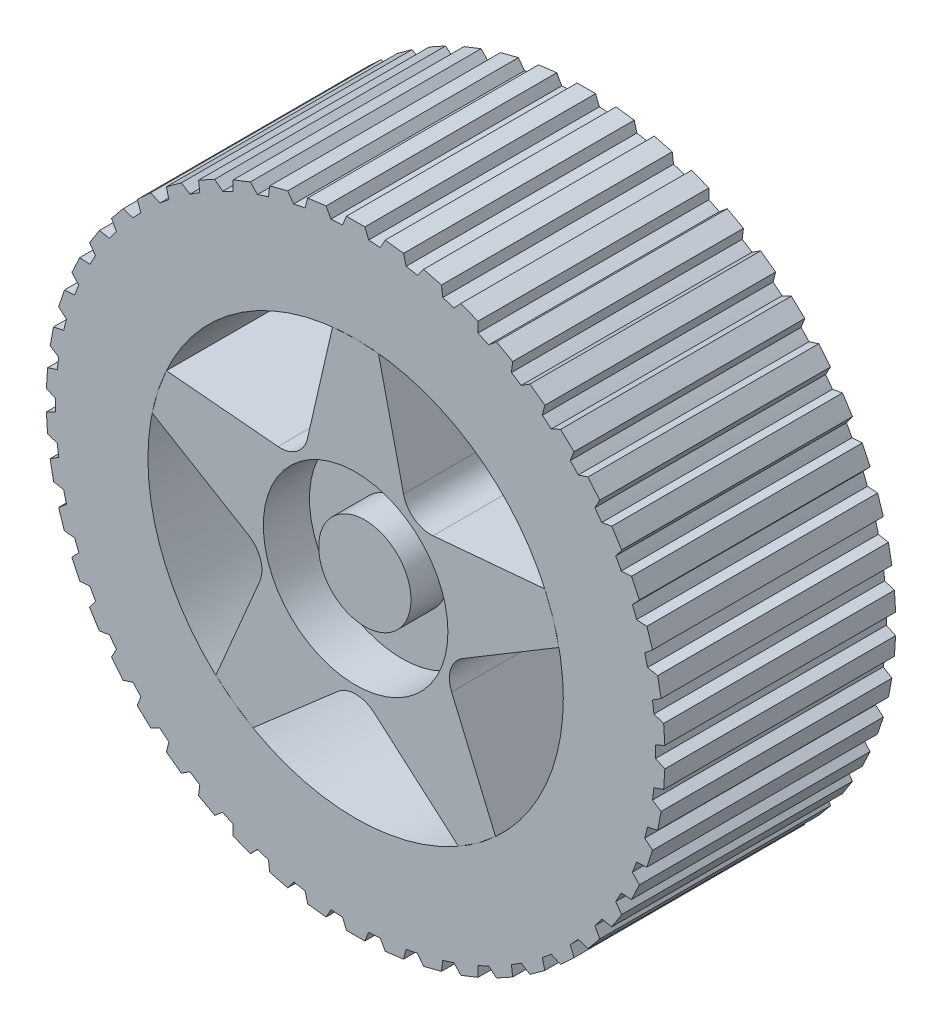
SolidWorks part; units mm, degrees
note: The reader was unsure of these and kept them because the rebuilt part matched: shared geometry of "Sketch1<13>", "Sketch1<14>".
ref_plane "Front Plane" through (0, 0, 0) normal (0, 0, 1) x (1, 0, 0)
ref_plane "Top Plane" through (0, 0, 0) normal (0, 1, 0) x (1, 0, 0)
ref_plane "Right Plane" through (0, 0, 0) normal (1, 0, 0) x (0, 0, -1)
sketch "Sketch1" plane through (0, 0, 0) normal (0, 0, 1) x (1, 0, 0)
  line L1 (0, 22.5) -> (-2.4961, 22.3611)
  line L3 (0, 22.5) -> (2.4961, 22.3611)
  line L4 (-2.4961, 22.3611) -> (-5.221, 10.5079)
  line L8 (2.4715, 22.3638) -> (5.1922, 10.5288)
  line L9 (20.4953, 9.2839) -> (8.3802, 8.2126)
  line L10 (21.3988, 6.9529) -> (20.4953, 9.2839)
  line L11 (21.3988, 6.9529) -> (22.038, 4.536)
  line L12 (22.033, 4.5602) -> (11.618, -1.6845)
  line L13 (15.163, -16.6233) -> (10.4003, -5.4322)
  line L14 (13.2252, -18.2029) -> (15.163, -16.6233)
  line L15 (13.2252, -18.2029) -> (11.1241, -19.5577)
  line L16 (11.1456, -19.5455) -> (1.9881, -11.5699)
  line L17 (-11.1241, -19.5577) -> (-1.9525, -11.5699)
  line L18 (-13.2252, -18.2029) -> (-11.1241, -19.5577)
  line L19 (-13.2252, -18.2029) -> (-15.163, -16.6233)
  line L20 (-15.1447, -16.64) -> (-10.3893, -5.4661)
  line L21 (-22.038, 4.536) -> (-11.607, -1.7184)
  line L22 (-21.3988, 6.9529) -> (-22.038, 4.536)
  line L23 (-21.3988, 6.9529) -> (-20.4953, 9.2839)
  line L24 (-20.5055, 9.2614) -> (-8.409, 8.1917)
  circle A0 centre (0, 0) radius 26
  circle A1 centre (0, 0) radius 32.5
  circle A2 centre (0, 0) radius 22.5
  circle A3 centre (0, 0) radius 5
  circle A4 centre (0, 0) radius 10
  circle A5 centre (0, 0) radius 10
  circle A6 centre (0, 0) radius 10
  circle A7 centre (0, 0) radius 10
  circle A8 centre (0, 0) radius 10
  arc A9 (-11.607, -1.7184) -> (-10.3893, -5.4661) centre (-13.1497, -4.2913) cw
  arc A10 (1.9881, -11.5699) -> (-1.9525, -11.5699) centre (0.0178, -13.8322) ccw
  arc A11 (10.4003, -5.4322) -> (11.618, -1.6845) centre (13.1607, -4.2575) cw
  arc A12 (8.3802, 8.2126) -> (5.1922, 10.5288) centre (8.116, 11.2009) cw
  arc A13 (-5.221, 10.5079) -> (-8.409, 8.1917) centre (-8.1448, 11.18) cw
  dimension "D1" = 5
  dimension "D2" = 3
extrude "Boss-Extrude3" add sketch "Sketch1" against normal blind 25 contours L4 A13 L24 L23 L22 L21 A9 L20 L19 L18 L17 A10 L16 L15 L14 L13 A11 L12 L11 L10 L9 A12 L8 L3 L1 A4 | A4 A3 | A3 | A1 A0 | A0 A2
extrude "Cut-Extrude8" cut sketch "Sketch1<13>" against normal blind 1 contours A3
sketch "Sketch1<13>" plane through (0, 0, 0) normal (0, 0, 1) x (1, 0, 0) same geometry as "Sketch1"
extrude "Cut-Extrude9" cut sketch "Sketch1<14>" against normal blind 5 contours A4 A3 | A3
sketch "Sketch1<14>" plane through (0, 0, 0) normal (0, 0, 1) x (1, 0, 0) same geometry as "Sketch1"
sketch "Sketch7" plane through (0, 0, 0) normal (0, 0, 1) x (1, 0, 0)
  line L0 (-1.6, 32) -> (1.6, 32)
  line L1 (1, 33.5) -> (-1, 33.5)
  line L2 (-1, 33.5) -> (-1.6, 32)
  line L3 (1, 33.5) -> (1.6, 32)
  line L4 (2.4233, 31.9482) -> (5.598, 31.5471)
  line L5 (5.1908, 33.1105) -> (3.2065, 33.3612)
  line L6 (3.2065, 33.3612) -> (2.4233, 31.9482)
  line L7 (5.1908, 33.1105) -> (5.598, 31.5471)
  line L8 (6.4083, 31.3926) -> (9.5078, 30.5968)
  line L9 (9.2997, 32.1988) -> (7.3625, 32.6962)
  line L10 (7.3625, 32.6962) -> (6.4083, 31.3926)
  line L11 (9.2997, 32.1988) -> (9.5078, 30.5968)
  line L12 (10.2923, 30.3418) -> (13.2676, 29.1638)
  line L13 (13.2619, 30.7794) -> (11.4024, 31.5156)
  line L14 (11.4024, 31.5156) -> (10.2923, 30.3418)
  line L15 (13.2619, 30.7794) -> (13.2676, 29.1638)
  line L16 (14.014, 28.8126) -> (16.8182, 27.271)
  line L17 (17.0151, 28.8745) -> (15.2624, 29.838)
  line L18 (15.2624, 29.838) -> (14.014, 28.8126)
  line L19 (17.0151, 28.8745) -> (16.8182, 27.271)
  line L20 (17.5147, 26.829) -> (20.1036, 24.9481)
  line L21 (20.4998, 26.5143) -> (18.8818, 27.6899)
  line L22 (18.8818, 27.6899) -> (17.5147, 26.829)
  line L23 (20.4998, 26.5143) -> (20.1036, 24.9481)
  line L24 (20.7392, 24.4223) -> (23.0719, 22.2317)
  line L25 (23.6613, 23.7359) -> (22.2034, 25.105)
  line L26 (22.2034, 25.105) -> (20.7392, 24.4223)
  line L27 (23.6613, 23.7359) -> (23.0719, 22.2317)
  line L28 (23.6365, 21.6304) -> (25.6763, 19.1647)
  line L29 (26.4496, 20.5832) -> (25.1748, 22.1242)
  line L30 (25.1748, 22.1242) -> (23.6365, 21.6304)
  line L31 (26.4496, 20.5832) -> (25.6763, 19.1647)
  line L32 (26.1612, 18.4974) -> (27.8758, 15.7955)
  line L33 (28.8208, 17.1059) -> (27.7492, 18.7945)
  line L34 (27.7492, 18.7945) -> (26.1612, 18.4974)
  line L35 (28.8208, 17.1059) -> (27.8758, 15.7955)
  line L36 (28.2732, 15.0727) -> (29.6357, 12.1772)
  line L37 (30.7375, 13.3588) -> (29.8859, 15.1684)
  line L38 (29.8859, 15.1684) -> (28.2732, 15.0727)
  line L39 (30.7375, 13.3588) -> (29.6357, 12.1772)
  line L40 (29.9394, 11.4102) -> (30.9282, 8.3669)
  line L41 (32.1694, 9.401) -> (31.5514, 11.3031)
  line L42 (31.5514, 11.3031) -> (29.9394, 11.4102)
  line L43 (32.1694, 9.401) -> (30.9282, 8.3669)
  line L44 (31.1334, 7.5679) -> (31.733, 4.4245)
  line L45 (33.094, 5.295) -> (32.7192, 7.2596)
  line L46 (32.7192, 7.2596) -> (31.1334, 7.5679)
  line L47 (33.094, 5.295) -> (31.733, 4.4245)
  line L48 (31.8364, 3.6061) -> (32.0373, 0.4125)
  line L49 (33.4967, 1.1055) -> (33.3711, 3.1015)
  line L50 (33.3711, 3.1015) -> (31.8364, 3.6061)
  line L51 (33.4967, 1.1055) -> (32.0373, 0.4125)
  line L52 (32.0373, -0.4125) -> (31.8364, -3.6061)
  line L53 (33.3711, -3.1015) -> (33.4967, -1.1055)
  line L54 (33.4967, -1.1055) -> (32.0373, -0.4125)
  line L55 (33.3711, -3.1015) -> (31.8364, -3.6061)
  line L56 (31.733, -4.4245) -> (31.1334, -7.5679)
  line L57 (32.7192, -7.2596) -> (33.094, -5.295)
  line L58 (33.094, -5.295) -> (31.733, -4.4245)
  line L59 (32.7192, -7.2596) -> (31.1334, -7.5679)
  line L60 (30.9282, -8.3669) -> (29.9394, -11.4102)
  line L61 (31.5514, -11.3031) -> (32.1694, -9.401)
  line L62 (32.1694, -9.401) -> (30.9282, -8.3669)
  line L63 (31.5514, -11.3031) -> (29.9394, -11.4102)
  line L64 (29.6357, -12.1772) -> (28.2732, -15.0727)
  line L65 (29.8859, -15.1684) -> (30.7375, -13.3588)
  line L66 (30.7375, -13.3588) -> (29.6357, -12.1772)
  line L67 (29.8859, -15.1684) -> (28.2732, -15.0727)
  line L68 (27.8758, -15.7955) -> (26.1612, -18.4974)
  line L69 (27.7492, -18.7945) -> (28.8208, -17.1059)
  line L70 (28.8208, -17.1059) -> (27.8758, -15.7955)
  line L71 (27.7492, -18.7945) -> (26.1612, -18.4974)
  line L72 (25.6763, -19.1647) -> (23.6365, -21.6304)
  line L73 (25.1748, -22.1242) -> (26.4496, -20.5832)
  line L74 (26.4496, -20.5832) -> (25.6763, -19.1647)
  line L75 (25.1748, -22.1242) -> (23.6365, -21.6304)
  line L76 (23.0719, -22.2317) -> (20.7392, -24.4223)
  line L77 (22.2034, -25.105) -> (23.6613, -23.7359)
  line L78 (23.6613, -23.7359) -> (23.0719, -22.2317)
  line L79 (22.2034, -25.105) -> (20.7392, -24.4223)
  line L80 (20.1036, -24.9481) -> (17.5147, -26.829)
  line L81 (18.8818, -27.6899) -> (20.4998, -26.5143)
  line L82 (20.4998, -26.5143) -> (20.1036, -24.9481)
  line L83 (18.8818, -27.6899) -> (17.5147, -26.829)
  line L84 (16.8182, -27.271) -> (14.014, -28.8126)
  line L85 (15.2624, -29.838) -> (17.0151, -28.8745)
  line L86 (17.0151, -28.8745) -> (16.8182, -27.271)
  line L87 (15.2624, -29.838) -> (14.014, -28.8126)
  line L88 (13.2676, -29.1638) -> (10.2923, -30.3418)
  line L89 (11.4024, -31.5156) -> (13.2619, -30.7794)
  line L90 (13.2619, -30.7794) -> (13.2676, -29.1638)
  line L91 (11.4024, -31.5156) -> (10.2923, -30.3418)
  line L92 (9.5078, -30.5968) -> (6.4083, -31.3926)
  line L93 (7.3625, -32.6962) -> (9.2997, -32.1988)
  line L94 (9.2997, -32.1988) -> (9.5078, -30.5968)
  line L95 (7.3625, -32.6962) -> (6.4083, -31.3926)
  line L96 (5.598, -31.5471) -> (2.4233, -31.9482)
  line L97 (3.2065, -33.3612) -> (5.1908, -33.1105)
  line L98 (5.1908, -33.1105) -> (5.598, -31.5471)
  line L99 (3.2065, -33.3612) -> (2.4233, -31.9482)
  line L100 (1.6, -32) -> (-1.6, -32)
  line L101 (-1, -33.5) -> (1, -33.5)
  line L102 (1, -33.5) -> (1.6, -32)
  line L103 (-1, -33.5) -> (-1.6, -32)
  line L104 (-2.4233, -31.9482) -> (-5.598, -31.5471)
  line L105 (-5.1908, -33.1105) -> (-3.2065, -33.3612)
  line L106 (-3.2065, -33.3612) -> (-2.4233, -31.9482)
  line L107 (-5.1908, -33.1105) -> (-5.598, -31.5471)
  line L108 (-6.4083, -31.3926) -> (-9.5078, -30.5968)
  line L109 (-9.2997, -32.1988) -> (-7.3625, -32.6962)
  line L110 (-7.3625, -32.6962) -> (-6.4083, -31.3926)
  line L111 (-9.2997, -32.1988) -> (-9.5078, -30.5968)
  line L112 (-10.2923, -30.3418) -> (-13.2676, -29.1638)
  line L113 (-13.2619, -30.7794) -> (-11.4024, -31.5156)
  line L114 (-11.4024, -31.5156) -> (-10.2923, -30.3418)
  line L115 (-13.2619, -30.7794) -> (-13.2676, -29.1638)
  line L116 (-14.014, -28.8126) -> (-16.8182, -27.271)
  line L117 (-17.0151, -28.8745) -> (-15.2624, -29.838)
  line L118 (-15.2624, -29.838) -> (-14.014, -28.8126)
  line L119 (-17.0151, -28.8745) -> (-16.8182, -27.271)
  line L120 (-17.5147, -26.829) -> (-20.1036, -24.9481)
  line L121 (-20.4998, -26.5143) -> (-18.8818, -27.6899)
  line L122 (-18.8818, -27.6899) -> (-17.5147, -26.829)
  line L123 (-20.4998, -26.5143) -> (-20.1036, -24.9481)
  line L124 (-20.7392, -24.4223) -> (-23.0719, -22.2317)
  line L125 (-23.6613, -23.7359) -> (-22.2034, -25.105)
  line L126 (-22.2034, -25.105) -> (-20.7392, -24.4223)
  line L127 (-23.6613, -23.7359) -> (-23.0719, -22.2317)
  line L128 (-23.6365, -21.6304) -> (-25.6763, -19.1647)
  line L129 (-26.4496, -20.5832) -> (-25.1748, -22.1242)
  line L130 (-25.1748, -22.1242) -> (-23.6365, -21.6304)
  line L131 (-26.4496, -20.5832) -> (-25.6763, -19.1647)
  line L132 (-26.1612, -18.4974) -> (-27.8758, -15.7955)
  line L133 (-28.8208, -17.1059) -> (-27.7492, -18.7945)
  line L134 (-27.7492, -18.7945) -> (-26.1612, -18.4974)
  line L135 (-28.8208, -17.1059) -> (-27.8758, -15.7955)
  line L136 (-28.2732, -15.0727) -> (-29.6357, -12.1772)
  line L137 (-30.7375, -13.3588) -> (-29.8859, -15.1684)
  line L138 (-29.8859, -15.1684) -> (-28.2732, -15.0727)
  line L139 (-30.7375, -13.3588) -> (-29.6357, -12.1772)
  line L140 (-29.9394, -11.4102) -> (-30.9282, -8.3669)
  line L141 (-32.1694, -9.401) -> (-31.5514, -11.3031)
  line L142 (-31.5514, -11.3031) -> (-29.9394, -11.4102)
  line L143 (-32.1694, -9.401) -> (-30.9282, -8.3669)
  line L144 (-31.1334, -7.5679) -> (-31.733, -4.4245)
  line L145 (-33.094, -5.295) -> (-32.7192, -7.2596)
  line L146 (-32.7192, -7.2596) -> (-31.1334, -7.5679)
  line L147 (-33.094, -5.295) -> (-31.733, -4.4245)
  line L148 (-31.8364, -3.6061) -> (-32.0373, -0.4125)
  line L149 (-33.4967, -1.1055) -> (-33.3711, -3.1015)
  line L150 (-33.3711, -3.1015) -> (-31.8364, -3.6061)
  line L151 (-33.4967, -1.1055) -> (-32.0373, -0.4125)
  line L152 (-32.0373, 0.4125) -> (-31.8364, 3.6061)
  line L153 (-33.3711, 3.1015) -> (-33.4967, 1.1055)
  line L154 (-33.4967, 1.1055) -> (-32.0373, 0.4125)
  line L155 (-33.3711, 3.1015) -> (-31.8364, 3.6061)
  line L156 (-31.733, 4.4245) -> (-31.1334, 7.5679)
  line L157 (-32.7192, 7.2596) -> (-33.094, 5.295)
  line L158 (-33.094, 5.295) -> (-31.733, 4.4245)
  line L159 (-32.7192, 7.2596) -> (-31.1334, 7.5679)
  line L160 (-30.9282, 8.3669) -> (-29.9394, 11.4102)
  line L161 (-31.5514, 11.3031) -> (-32.1694, 9.401)
  line L162 (-32.1694, 9.401) -> (-30.9282, 8.3669)
  line L163 (-31.5514, 11.3031) -> (-29.9394, 11.4102)
  line L164 (-29.6357, 12.1772) -> (-28.2732, 15.0727)
  line L165 (-29.8859, 15.1684) -> (-30.7375, 13.3588)
  line L166 (-30.7375, 13.3588) -> (-29.6357, 12.1772)
  line L167 (-29.8859, 15.1684) -> (-28.2732, 15.0727)
  line L168 (-27.8758, 15.7955) -> (-26.1612, 18.4974)
  line L169 (-27.7492, 18.7945) -> (-28.8208, 17.1059)
  line L170 (-28.8208, 17.1059) -> (-27.8758, 15.7955)
  line L171 (-27.7492, 18.7945) -> (-26.1612, 18.4974)
  line L172 (-25.6763, 19.1647) -> (-23.6365, 21.6304)
  line L173 (-25.1748, 22.1242) -> (-26.4496, 20.5832)
  line L174 (-26.4496, 20.5832) -> (-25.6763, 19.1647)
  line L175 (-25.1748, 22.1242) -> (-23.6365, 21.6304)
  line L176 (-23.0719, 22.2317) -> (-20.7392, 24.4223)
  line L177 (-22.2034, 25.105) -> (-23.6613, 23.7359)
  line L178 (-23.6613, 23.7359) -> (-23.0719, 22.2317)
  line L179 (-22.2034, 25.105) -> (-20.7392, 24.4223)
  line L180 (-20.1036, 24.9481) -> (-17.5147, 26.829)
  line L181 (-18.8818, 27.6899) -> (-20.4998, 26.5143)
  line L182 (-20.4998, 26.5143) -> (-20.1036, 24.9481)
  line L183 (-18.8818, 27.6899) -> (-17.5147, 26.829)
  line L184 (-16.8182, 27.271) -> (-14.014, 28.8126)
  line L185 (-15.2624, 29.838) -> (-17.0151, 28.8745)
  line L186 (-17.0151, 28.8745) -> (-16.8182, 27.271)
  line L187 (-15.2624, 29.838) -> (-14.014, 28.8126)
  line L188 (-13.2676, 29.1638) -> (-10.2923, 30.3418)
  line L189 (-11.4024, 31.5156) -> (-13.2619, 30.7794)
  line L190 (-13.2619, 30.7794) -> (-13.2676, 29.1638)
  line L191 (-11.4024, 31.5156) -> (-10.2923, 30.3418)
  line L192 (-9.5078, 30.5968) -> (-6.4083, 31.3926)
  line L193 (-7.3625, 32.6962) -> (-9.2997, 32.1988)
  line L194 (-9.2997, 32.1988) -> (-9.5078, 30.5968)
  line L195 (-7.3625, 32.6962) -> (-6.4083, 31.3926)
  line L196 (-5.598, 31.5471) -> (-2.4233, 31.9482)
  line L197 (-3.2065, 33.3612) -> (-5.1908, 33.1105)
  line L198 (-5.1908, 33.1105) -> (-5.598, 31.5471)
  line L199 (-3.2065, 33.3612) -> (-2.4233, 31.9482)
  dimension "D1" = 50
extrude "Boss-Extrude4" add sketch "Sketch7" against normal blind 25
sketch "Sketch8" plane through (0, 0, -25) normal (0, 0, -1) x (-1, 0, 0)
  circle A0 centre (0, 0) radius 22.5
extrude "Cut-Extrude10" cut sketch "Sketch8" against normal blind 10
sketch "Sketch9" plane through (0, 0, -15) normal (0, 0, -1) x (-1, 0, 0)
  circle A0 centre (0, 0) radius 5
